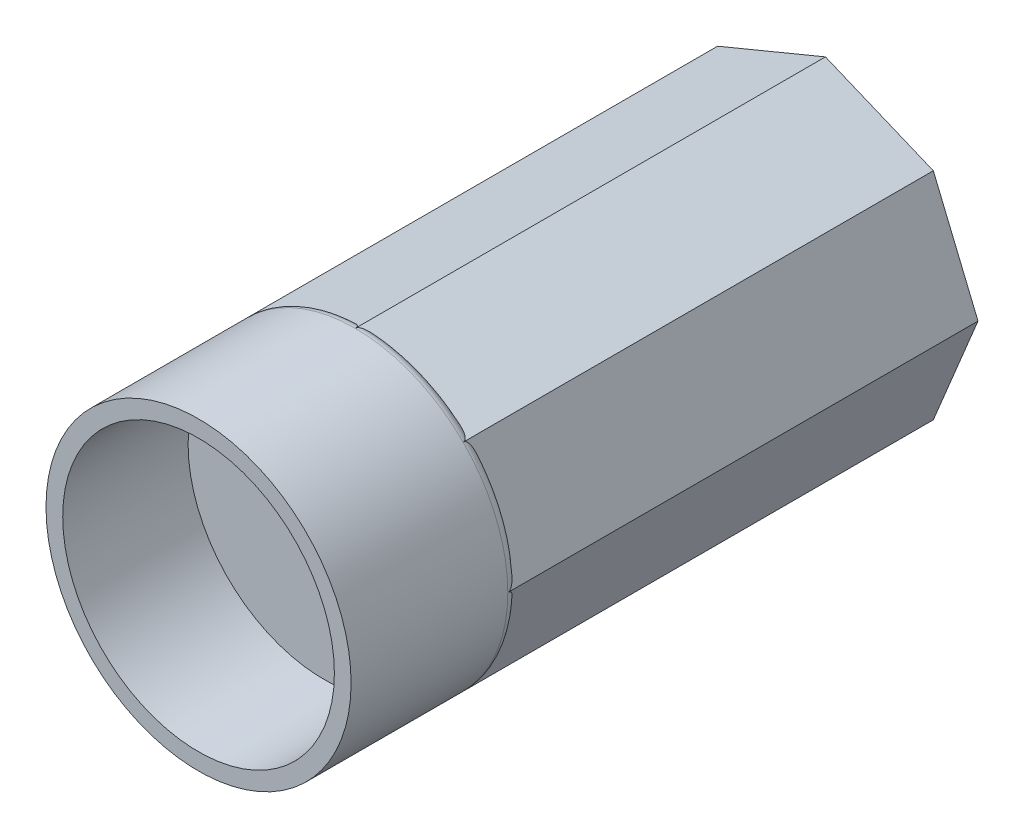
SolidWorks part; units mm, degrees
ref_plane "Front Plane" through (0, 0, 0) normal (0, 0, 1) x (1, 0, 0)
ref_plane "Top Plane" through (0, 0, 0) normal (0, 1, 0) x (1, 0, 0)
ref_plane "Right Plane" through (0, 0, 0) normal (1, 0, 0) x (0, 0, -1)
sketch "Sketch1" plane through (0, 0, 0) normal (0, 0, 1) x (1, 0, 0)
  circle A0 centre (0, 0) radius 7.3
extrude "Boss-Extrude1" add sketch "Sketch1" along normal blind 30
sketch "Sketch2" plane through (0, 0, 30) normal (0, 0, 1) x (1, 0, 0)
  circle A0 centre (0, 0) radius 6.5
extrude "Cut-Extrude1" cut sketch "Sketch2" against normal blind 6
sketch "Sketch3" plane through (0, 0, 0) normal (0, 0, -1) x (-1, 0, 0)
  line L7 (7.3, 0) -> (5.1619, 5.1619)
  line L8 (5.1619, 5.1619) -> (0, 7.3)
  line L9 (0, 7.3) -> (-5.1619, 5.1619)
  line L10 (-5.1619, 5.1619) -> (-7.3, 0)
  line L11 (-7.3, 0) -> (-5.1619, -5.1619)
  line L12 (-5.1619, -5.1619) -> (0, -7.3)
  line L13 (0, -7.3) -> (5.1619, -5.1619)
  line L14 (5.1619, -5.1619) -> (7.3, 0)
  circle A0 centre (0, 0) radius 6.7443 construction
extrude "Cut-Extrude3" cut sketch "Sketch3" against normal offset from surface (22 mm away) 2 flip side to cut up to face at (6.5, 0, 24)
fillet "Fillet2" radius 0.5 8 edges at (6.7443, -2.7936, 22) (6.7443, 2.7936, 22) (2.7936, 6.7443, 22) (-2.7936, 6.7443, 22) (-6.7443, 2.7936, 22) (-6.7443, -2.7936, 22) (-2.7936, -6.7443, 22) (2.7936, -6.7443, 22)
